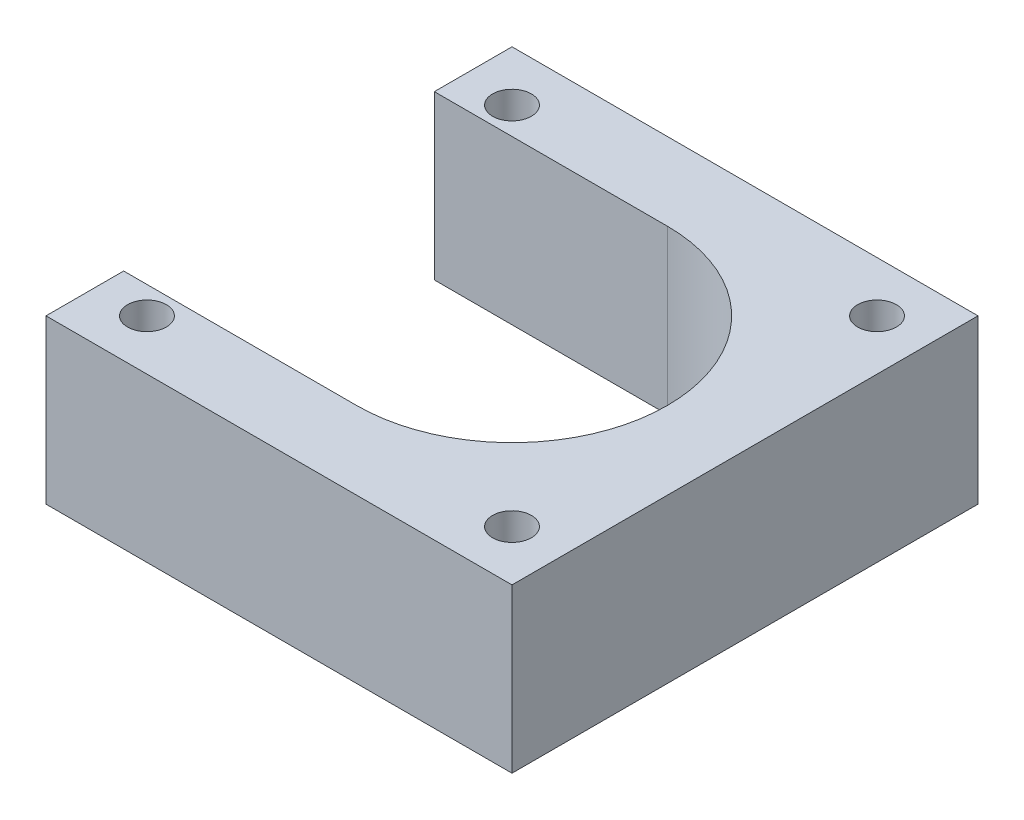
SolidWorks part; units mm, degrees
ref_plane "Front Plane" through (0, 0, 0) normal (0, 0, 1) x (1, 0, 0)
ref_plane "Top Plane" through (0, 0, 0) normal (0, 1, 0) x (1, 0, 0)
ref_plane "Right Plane" through (0, 0, 0) normal (1, 0, 0) x (0, 0, -1)
sketch "Sketch1" plane through (0, 0, 0) normal (0, 1, 0) x (1, 0, 0)
  line L0 (0, 20) -> (-30, 20)
  line L1 (-30, 30) -> (30, 30)
  line L2 (-30, 30) -> (-30, 20)
  line L3 (-30, -30) -> (30, -30)
  line L4 (30, 30) -> (30, -30)
  line L5 (-30, 30) -> (30, -30) construction
  line L6 (-30, -30) -> (30, 30) construction
  line L7 (0, -20) -> (-30, -20)
  line L8 (-30, -20) -> (-30, -30)
  circle A0 centre (-23.5, 23.5) radius 2.5
  circle A1 centre (23.5, 23.5) radius 2.5
  circle A2 centre (-23.5, -23.5) radius 2.5
  circle A3 centre (23.5, -23.5) radius 2.5
  arc A4 (0, -20) -> (0, 20) centre (0, 0) ccw
  point P0 (0, 0)
  dimension "D3" = 5
  dimension "D8" = 40
  dimension "D1" = 60
  dimension "D2" = 60
  dimension "D4" = 47
  dimension "D5" = 47
  dimension "D6" = 23.5
  dimension "D7" = 23.5
extrude "Boss-Extrude1" add sketch "Sketch1" along normal blind 21
